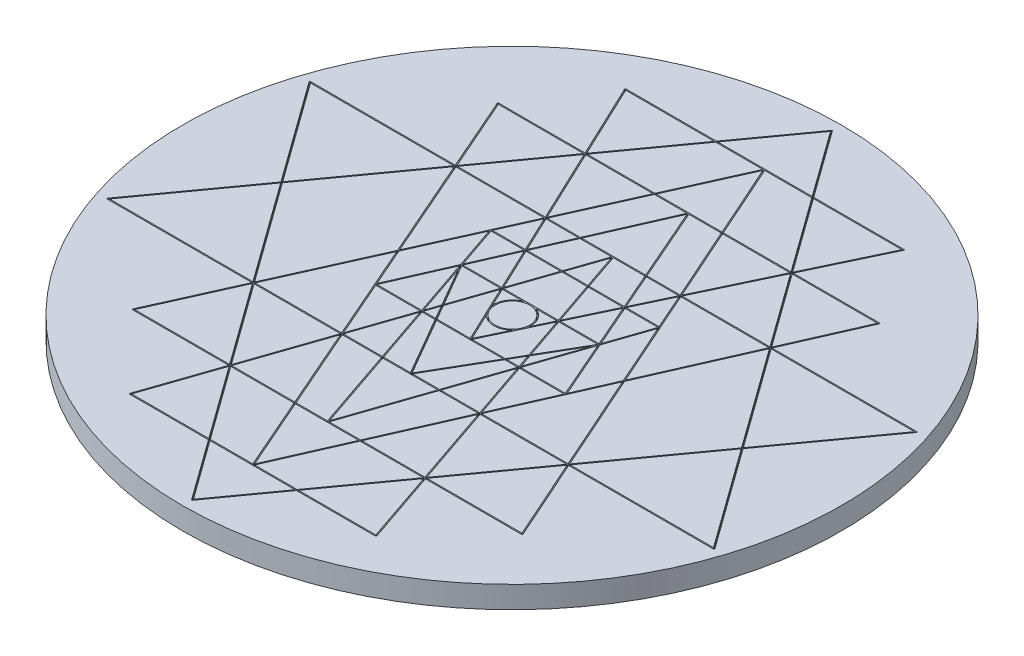
SolidWorks part; units mm, degrees
ref_plane "Front Plane" through (0, 0, 0) normal (0, 0, 1) x (1, 0, 0)
ref_plane "Top Plane" through (0, 0, 0) normal (0, 1, 0) x (1, 0, 0)
ref_plane "Right Plane" through (0, 0, 0) normal (1, 0, 0) x (0, 0, -1)
sketch "Sketch1" plane through (0, 0, 0) normal (0, 1, 0) x (1, 0, 0)
  line L7 (-124.1807, -41.4) -> (124.1807, -41.4)
  line L8 (124.1807, -41.4) -> (0, 130.9)
  line L12 (0, 130.9) -> (-124.1807, -41.4)
  line L13 (-124.1807, 41.4) -> (0, -130.9)
  line L25 (0, -130.9) -> (124.1807, 41.4)
  line L26 (124.1807, 41.4) -> (-124.1807, 41.4)
  line L27 (0, 130.9) -> (0, -130.9) construction
  line L28 (-130.9, 0) -> (130.9, 0) construction
  line L29 (56.9436, 103.3919) -> (-56.9436, 103.3919)
  line L30 (50.3636, -106.0481) -> (-50.3636, -106.0481)
  line L31 (0, 103.3919) -> (-79.6958, -75.4988)
  line L32 (0, 103.3919) -> (79.6958, -75.4988)
  line L33 (0, -106.0481) -> (-78.0225, 72.2994)
  line L34 (-78.0225, 72.2994) -> (0, -106.0481)
  line L35 (0, -106.0481) -> (78.0225, 72.2994)
  line L36 (50.3636, -106.0481) -> (0, 41.4)
  line L37 (0, 41.4) -> (-50.3636, -106.0481)
  line L38 (-38.9651, -16.9798) -> (38.9651, -16.9798)
  line L39 (56.9436, 103.3919) -> (0, -16.9798)
  line L40 (0, -16.9798) -> (-56.9436, 103.3919)
  line L41 (-78.0225, 72.2994) -> (78.0225, 72.2994)
  line L42 (0, 72.2994) -> (-38.9651, -16.9798)
  line L43 (0, 72.2994) -> (38.9651, -16.9798)
  line L44 (-34.5395, 25.8623) -> (34.5395, 25.8623)
  line L45 (-79.6958, -75.4988) -> (79.6958, -75.4988)
  line L46 (-34.5395, 25.8623) -> (0, -75.4988)
  line L47 (0, -75.4988) -> (34.5395, 25.8623)
  line L48 (-28.2818, 7.4983) -> (28.2818, 7.4983)
  line L49 (28.2818, 7.4983) -> (0, -41.4)
  line L50 (0, -41.4) -> (-28.2818, 7.4983)
  line L51 (0, -130.9) -> (124.1807, 41.4) construction
  line L52 (-0.2028, -130.7538) -> (123.9779, 41.5462)
  line L53 (0.2028, -131.0462) -> (124.3835, 41.2538)
  line L54 (124.1807, 41.4) -> (-124.1807, 41.4) construction
  line L55 (124.1807, 41.15) -> (-124.1807, 41.15)
  line L56 (124.1807, 41.65) -> (-124.1807, 41.65)
  line L57 (-124.1807, 41.4) -> (0, -130.9) construction
  line L58 (-123.9779, 41.5462) -> (0.2028, -130.7538)
  line L59 (-124.3835, 41.2538) -> (-0.2028, -131.0462)
  line L60 (0, 130.9) -> (124.1807, -41.4) construction
  line L61 (0.2028, 131.0462) -> (124.3835, -41.2538)
  line L62 (-0.2028, 130.7538) -> (123.9779, -41.5462)
  line L63 (0, 130.9) -> (-124.1807, -41.4) construction
  line L64 (0.2028, 130.7538) -> (-123.9779, -41.5462)
  line L65 (-0.2028, 131.0462) -> (-124.3835, -41.2538)
  line L66 (-124.1807, -41.4) -> (124.1807, -41.4) construction
  line L67 (-124.1807, -41.15) -> (124.1807, -41.15)
  line L68 (-124.1807, -41.65) -> (124.1807, -41.65)
  line L69 (50.3636, -106.0481) -> (0, 41.4) construction
  line L70 (50.1271, -106.1289) -> (-0.2366, 41.3192)
  line L71 (50.6002, -105.9673) -> (0.2366, 41.4808)
  line L72 (0, 41.4) -> (-50.3636, -106.0481) construction
  line L73 (0.2366, 41.3192) -> (-50.1271, -106.1289)
  line L74 (-0.2366, 41.4808) -> (-50.6002, -105.9673)
  line L75 (-50.3636, -106.0481) -> (50.3636, -106.0481) construction
  line L76 (-50.3636, -105.7981) -> (50.3636, -105.7981)
  line L77 (-50.3636, -106.2981) -> (50.3636, -106.2981)
  line L78 (79.6958, -75.4988) -> (0, 103.3919) construction
  line L79 (79.4674, -75.6005) -> (-0.2284, 103.2902)
  line L80 (79.9242, -75.3971) -> (0.2284, 103.4937)
  line L81 (0, 103.3919) -> (-79.6958, -75.4988) construction
  line L82 (0.2284, 103.2902) -> (-79.4674, -75.6005)
  line L83 (-0.2284, 103.4937) -> (-79.9242, -75.3971)
  line L84 (-79.6958, -75.4988) -> (79.6958, -75.4988) construction
  line L85 (-79.6958, -75.2488) -> (79.6958, -75.2488)
  line L86 (-79.6958, -75.7488) -> (79.6958, -75.7488)
  line L87 (0, -106.0481) -> (78.0225, 72.2994) construction
  line L88 (-0.229, -105.9479) -> (77.7935, 72.3996)
  line L89 (0.229, -106.1483) -> (78.2515, 72.1992)
  line L90 (78.0225, 72.2994) -> (-78.0225, 72.2994) construction
  line L91 (78.0225, 72.0494) -> (-78.0225, 72.0494)
  line L92 (78.0225, 72.5494) -> (-78.0225, 72.5494)
  line L93 (-78.0225, 72.2994) -> (0, -106.0481) construction
  line L94 (-77.7935, 72.3996) -> (0.229, -105.9479)
  line L95 (-78.2515, 72.1992) -> (-0.229, -106.1483)
  line L96 (0, -75.4988) -> (34.5395, 25.8623) construction
  line L97 (-0.2366, -75.4182) -> (34.3028, 25.9429)
  line L98 (0.2366, -75.5794) -> (34.7761, 25.7816)
  line L99 (34.5395, 25.8623) -> (-34.5395, 25.8623) construction
  line L100 (34.5395, 25.6123) -> (-34.5395, 25.6123)
  line L101 (34.5395, 26.1123) -> (-34.5395, 26.1123)
  line L102 (-34.5395, 25.8623) -> (0, -75.4988) construction
  line L103 (-34.3028, 25.9429) -> (0.2366, -75.4182)
  line L104 (-34.7761, 25.7816) -> (-0.2366, -75.5794)
  line L105 (38.9651, -16.9798) -> (-38.9651, -16.9798) construction
  line L106 (38.9651, -17.2298) -> (-38.9651, -17.2298)
  line L107 (38.9651, -16.7298) -> (-38.9651, -16.7298)
  line L108 (-38.9651, -16.9798) -> (0, 72.2994) construction
  line L109 (-39.1942, -16.8798) -> (-0.2291, 72.3994)
  line L110 (-38.736, -17.0798) -> (0.2291, 72.1994)
  line L111 (0, 72.2994) -> (38.9651, -16.9798) construction
  line L112 (0.2291, 72.3994) -> (39.1942, -16.8798)
  line L113 (-0.2291, 72.1994) -> (38.736, -17.0798)
  line L114 (56.9436, 103.3919) -> (0, -16.9798) construction
  line L115 (57.1695, 103.285) -> (0.226, -17.0867)
  line L116 (56.7176, 103.4988) -> (-0.226, -16.8729)
  line L117 (0, -16.9798) -> (-56.9436, 103.3919) construction
  line L118 (-0.226, -17.0867) -> (-57.1695, 103.285)
  line L119 (0.226, -16.8729) -> (-56.7176, 103.4988)
  line L120 (-56.9436, 103.3919) -> (56.9436, 103.3919) construction
  line L121 (-56.9436, 103.6419) -> (56.9436, 103.6419)
  line L122 (-56.9436, 103.1419) -> (56.9436, 103.1419)
  line L123 (-28.2818, 7.4983) -> (0, -41.4) construction
  line L124 (-28.0654, 7.6235) -> (0.2164, -41.2748)
  line L125 (-28.4982, 7.3732) -> (-0.2164, -41.5252)
  line L126 (0, -41.4) -> (28.2818, 7.4983) construction
  line L127 (-0.2164, -41.2748) -> (28.0654, 7.6235)
  line L128 (0.2164, -41.5252) -> (28.4982, 7.3732)
  line L129 (28.2818, 7.4983) -> (-28.2818, 7.4983) construction
  line L130 (28.2818, 7.2483) -> (-28.2818, 7.2483)
  line L131 (28.2818, 7.7483) -> (-28.2818, 7.7483)
  circle A1 centre (0, 0) radius 130.9
  circle A3 centre (0, 0.1662) radius 7.3321
  arc A4 (-0.2028, -130.7538) -> (0.2028, -131.0462) centre (0, -130.9) ccw
  arc A5 (124.3835, 41.2538) -> (123.9779, 41.5462) centre (124.1807, 41.4) ccw
  arc A6 (124.1807, 41.15) -> (124.1807, 41.65) centre (124.1807, 41.4) ccw
  arc A7 (-124.1807, 41.65) -> (-124.1807, 41.15) centre (-124.1807, 41.4) ccw
  arc A8 (-123.9779, 41.5462) -> (-124.3835, 41.2538) centre (-124.1807, 41.4) ccw
  arc A9 (-0.2028, -131.0462) -> (0.2028, -130.7538) centre (0, -130.9) ccw
  arc A10 (0.2028, 131.0462) -> (-0.2028, 130.7538) centre (0, 130.9) ccw
  arc A11 (123.9779, -41.5462) -> (124.3835, -41.2538) centre (124.1807, -41.4) ccw
  arc A12 (0.2028, 130.7538) -> (-0.2028, 131.0462) centre (0, 130.9) ccw
  arc A13 (-124.3835, -41.2538) -> (-123.9779, -41.5462) centre (-124.1807, -41.4) ccw
  arc A14 (-124.1807, -41.15) -> (-124.1807, -41.65) centre (-124.1807, -41.4) ccw
  arc A15 (124.1807, -41.65) -> (124.1807, -41.15) centre (124.1807, -41.4) ccw
  arc A16 (50.1271, -106.1289) -> (50.6002, -105.9673) centre (50.3636, -106.0481) ccw
  arc A17 (0.2366, 41.4808) -> (-0.2366, 41.3192) centre (0, 41.4) ccw
  arc A18 (0.2366, 41.3192) -> (-0.2366, 41.4808) centre (0, 41.4) ccw
  arc A19 (-50.6002, -105.9673) -> (-50.1271, -106.1289) centre (-50.3636, -106.0481) ccw
  arc A20 (-50.3636, -105.7981) -> (-50.3636, -106.2981) centre (-50.3636, -106.0481) ccw
  arc A21 (50.3636, -106.2981) -> (50.3636, -105.7981) centre (50.3636, -106.0481) ccw
  arc A22 (79.4674, -75.6005) -> (79.9242, -75.3971) centre (79.6958, -75.4988) ccw
  arc A23 (0.2284, 103.4937) -> (-0.2284, 103.2902) centre (0, 103.3919) ccw
  arc A24 (0.2284, 103.2902) -> (-0.2284, 103.4937) centre (0, 103.3919) ccw
  arc A25 (-79.9242, -75.3971) -> (-79.4674, -75.6005) centre (-79.6958, -75.4988) ccw
  arc A26 (-79.6958, -75.2488) -> (-79.6958, -75.7488) centre (-79.6958, -75.4988) ccw
  arc A27 (79.6958, -75.7488) -> (79.6958, -75.2488) centre (79.6958, -75.4988) ccw
  arc A28 (-0.229, -105.9479) -> (0.229, -106.1483) centre (0, -106.0481) ccw
  arc A29 (78.2515, 72.1992) -> (77.7935, 72.3996) centre (78.0225, 72.2994) ccw
  arc A30 (78.0225, 72.0494) -> (78.0225, 72.5494) centre (78.0225, 72.2994) ccw
  arc A31 (-78.0225, 72.5494) -> (-78.0225, 72.0494) centre (-78.0225, 72.2994) ccw
  arc A32 (-77.7935, 72.3996) -> (-78.2515, 72.1992) centre (-78.0225, 72.2994) ccw
  arc A33 (-0.229, -106.1483) -> (0.229, -105.9479) centre (0, -106.0481) ccw
  arc A34 (-0.2366, -75.4182) -> (0.2366, -75.5794) centre (0, -75.4988) ccw
  arc A35 (34.7761, 25.7816) -> (34.3028, 25.9429) centre (34.5395, 25.8623) ccw
  arc A36 (34.5395, 25.6123) -> (34.5395, 26.1123) centre (34.5395, 25.8623) ccw
  arc A37 (-34.5395, 26.1123) -> (-34.5395, 25.6123) centre (-34.5395, 25.8623) ccw
  arc A38 (-34.3028, 25.9429) -> (-34.7761, 25.7816) centre (-34.5395, 25.8623) ccw
  arc A39 (-0.2366, -75.5794) -> (0.2366, -75.4182) centre (0, -75.4988) ccw
  arc A40 (38.9651, -17.2298) -> (38.9651, -16.7298) centre (38.9651, -16.9798) ccw
  arc A41 (-38.9651, -16.7298) -> (-38.9651, -17.2298) centre (-38.9651, -16.9798) ccw
  arc A42 (-39.1942, -16.8798) -> (-38.736, -17.0798) centre (-38.9651, -16.9798) ccw
  arc A43 (0.2291, 72.1994) -> (-0.2291, 72.3994) centre (0, 72.2994) ccw
  arc A44 (0.2291, 72.3994) -> (-0.2291, 72.1994) centre (0, 72.2994) ccw
  arc A45 (38.736, -17.0798) -> (39.1942, -16.8798) centre (38.9651, -16.9798) ccw
  arc A46 (57.1695, 103.285) -> (56.7176, 103.4988) centre (56.9436, 103.3919) ccw
  arc A47 (-0.226, -16.8729) -> (0.226, -17.0867) centre (0, -16.9798) ccw
  arc A48 (-0.226, -17.0867) -> (0.226, -16.8729) centre (0, -16.9798) ccw
  arc A49 (-56.7176, 103.4988) -> (-57.1695, 103.285) centre (-56.9436, 103.3919) ccw
  arc A50 (-56.9436, 103.6419) -> (-56.9436, 103.1419) centre (-56.9436, 103.3919) ccw
  arc A51 (56.9436, 103.1419) -> (56.9436, 103.6419) centre (56.9436, 103.3919) ccw
  arc A52 (-28.0654, 7.6235) -> (-28.4982, 7.3732) centre (-28.2818, 7.4983) ccw
  arc A53 (-0.2164, -41.5252) -> (0.2164, -41.2748) centre (0, -41.4) ccw
  arc A54 (-0.2164, -41.2748) -> (0.2164, -41.5252) centre (0, -41.4) ccw
  arc A55 (28.4982, 7.3732) -> (28.0654, 7.6235) centre (28.2818, 7.4983) ccw
  arc A56 (28.2818, 7.2483) -> (28.2818, 7.7483) centre (28.2818, 7.4983) ccw
  arc A57 (-28.2818, 7.7483) -> (-28.2818, 7.2483) centre (-28.2818, 7.4983) ccw
  circle A60 centre (0, 0) radius 135
  circle A61 centre (0, 0.1662) radius 7.0821
  circle A62 centre (0, 0.1662) radius 7.5821
  point P2 (27.6174, 41.4)
  point P11 (-94.3427, 0)
  point P12 (94.3427, 0)
  point P16 (0, 103.3919)
  point P19 (0, -106.0481)
  point P21 (-64.5048, -41.4)
  point P22 (-64.5048, 41.4)
  point P23 (64.5048, 41.4)
  point P24 (64.5048, -41.4)
  point P25 (-28.2819, -41.4)
  point P30 (28.2819, -41.4)
  point P34 (-27.6174, 41.4)
  point P35 (42.2348, 72.2994)
  point P36 (-20.2671, 25.8623)
  point P37 (-42.2348, 72.2994)
  point P41 (20.2671, 25.8623)
  point P42 (19.9407, -16.9798)
  point P43 (-19.9407, -16.9798)
  point P46 (39.929, -75.4988)
  point P47 (-39.929, -75.4988)
  point P48 (11.5797, 7.4983)
  point P51 (-11.5797, 7.4983)
  point P54 (62.0904, -44.75)
  point P60 (0, 41.4)
  point P67 (-62.0904, -44.75)
  point P74 (62.0904, 44.75)
  point P79 (-62.0904, 44.75)
  point P85 (0, -41.4)
  point P92 (25.1818, -32.324)
  point P97 (-25.1818, -32.324)
  point P103 (0, -106.0481)
  point P110 (39.8479, 13.9466)
  point P115 (-39.8479, 13.9466)
  point P121 (0, -75.4988)
  point P128 (124.3269, 41.6028)
  point P129 (39.0113, -16.8743)
  point P134 (0, 72.2994)
  point P140 (-39.0113, -16.8743)
  point P147 (17.2697, -24.8183)
  point P152 (0, 25.8623)
  point P158 (-17.2697, -24.8183)
  point P165 (0, -16.9798)
  point P170 (-19.4825, 27.6598)
  point P176 (19.4825, 27.6598)
  point P183 (28.4718, 43.2061)
  point P188 (-28.4718, 43.2061)
  point P194 (0, 103.3919)
  point P201 (-14.1409, -16.9508)
  point P206 (14.1409, -16.9508)
  point P212 (0, 7.4983)
  dimension "D1" = 261.8
  dimension "D3" = 209.44
  dimension "D5" = 270
  dimension "D2" = 82.8
  dimension "D4" = 0.5
extrude "Boss-Extrude3" add sketch "Sketch1" along normal blind 9 contours A61 | A62 L116 L130 | A62 L130 L119 | A62 L119 L116 | L107 L127 L70 L115 | L73 L124 L107 L118 | L125 L73 L107 | L128 L107 L70 | L128 L71 L97 | L127 L130 L71 | L74 L130 L124 | L125 L103 L74 | L131 L118 L110 | L110 L107 L104 | L131 L70 L100 L73 | L119 L74 L100 | L116 L100 L71 | L131 L113 L115 | L113 L98 L107 | L128 L67 L97 L106 | L124 L127 L106 | L125 L106 L103 L67 | L104 L73 L67 | L74 L106 L94 | L94 L109 L104 L82 | L103 L109 L100 | L101 L70 L73 | L113 L55 L71 L101 | L100 L112 L97 | L98 L112 L88 L79 | L88 L106 L71 | L98 L67 L70 | L98 L85 L88 L68 | L71 L52 L68 | L89 L67 L79 | L89 L85 L70 | L68 L103 L97 | L104 L68 L94 L85 | L95 L73 L85 | L74 L68 L58 | L82 L85 L59 | L53 L85 L79 | L95 L82 L67 | L95 L64 L58 L83 | L64 L67 L59 | L65 L55 L58 | L55 L94 L83 | L56 L118 L64 | L91 L94 L65 | L119 L83 L91 | L56 L109 L91 L82 | L119 L109 L55 | L101 L118 L82 | L110 L101 L74 L55 | L113 L110 L56 | L91 L112 L56 L79 | L116 L55 L112 | L116 L91 L80 | L62 L115 L56 | L79 L115 L101 | L80 L88 L55 | L89 L80 L52 L62 | L53 L67 L62 | L55 L61 L52 | L88 L91 L61 | L122 L61 L116 | L122 L80 L92 L62 | L64 L121 L62 | L92 L79 L82 | L122 L64 L92 L83 | L122 L119 L65 | A49 L121 L65 A1 L56 L95 A31 L92 L118 | L59 A1 L65 | A25 L83 L68 A1 L59 L77 A19 L74 L86 | L73 L76 L59 | L95 L86 L58 L76 | L77 L58 L52 | L86 L94 L88 | L89 L76 L52 L86 | L53 L76 L70 | A22 L86 L71 A16 L77 L53 A1 L68 L80 | L61 A1 L53 | A60 A13 L65 A1 L59 A7 L56 A10 L61 A5 L53 A11 L68 A4 | A46 L115 L92 A29 L89 L56 A1 L61 L121 region at (-94.3427, 0, 27.5759) region at (-117.2906, 0, 0) region at (-69.7522, 0, 84.0712) region at (-68.3646, 0, 0.0484) region at (-94.3427, 0, -27.5759) region at (-61.3938, 0, 64.1322) region at (-69.6322, 0, -83.9176) region at (-36.0875, 0, 95.8779) region at (0, 0, 114.3562) region at (69.7522, 0, 84.0712) region at (-44.219, 0, 52.7533) region at (-46.3382, 0, 27.7651) region at (-18.3535, 0, 89.7893) region at (-46.1172, 0, -27.5142) region at (36.0875, 0, 95.8779) region at (-37.0679, 0, -4.067) region at (-44.7694, 0, -51.7032) region at (-61.6049, 0, -62.0002) region at (69.6322, 0, -83.9176) region at (-39.6842, 0, -93.0244) region at (0, 0, -112.5854) region at (18.3535, 0, 89.7893) region at (117.2906, 0, 0) region at (-29.0612, 0, 25.0568) region at (-27.1931, 0, 64.1957) region at (61.3938, 0, 64.1322) region at (94.3427, 0, 27.5759) region at (-13.5566, 0, 57.8209) region at (-19.9473, 0, 33.3514) region at (-19.4929, 0, -86.9332) region at (0, 0, 85.6406) region at (-27.4756, 0, -31.0085) region at (39.6842, 0, -93.0244) region at (27.1931, 0, 64.1957) region at (44.219, 0, 52.7533) region at (68.3646, 0, 0.0484) region at (94.3427, 0, -27.5759) region at (-29.0613, 0, 8.884) region at (-27.6974, 0, -19.8046) region at (-27.9003, 0, -62.0326) region at (19.4929, 0, -86.9332) region at (46.3382, 0, 27.7651) region at (-10.7957, 0, 30.5776) region at (0, 0, 52.6746) region at (-20.4555, 0, -36.2554) region at (-13.7611, 0, -56.7978) region at (61.6049, 0, -62.0002) region at (13.5566, 0, 57.8209) region at (-17.2903, 0, 14.906) region at (0, 0, -82.6255) region at (46.1172, 0, -27.5142) region at (-21.7399, 0, 7.2393) region at (-20.0441, 0, -13.585) region at (44.7694, 0, -51.7032) region at (27.9003, 0, -62.0326) region at (37.0679, 0, -4.067) region at (-9.8115, 0, -33.5005) region at (0, 0, -51.6582) region at (29.0612, 0, 25.0568) region at (0, 0, 25.1201)
sketch "Sketch4" plane through (0, 0, 0) normal (0, -1, 0) x (1, 0, 0)
  circle A0 centre (0, 0) radius 135
extrude "Boss-Extrude4" add sketch "Sketch4" against normal blind 8
sketch "Sketch5" plane through (0, 8, 0) normal (0, 1, 0) x (1, 0, 0)
  line L0 (-124.1807, 41.4) -> (124.1807, 41.4) construction
  line L1 (124.1807, 41.4) -> (0, -130.9) construction
  line L2 (0, -130.9) -> (-124.1807, 41.4) construction
  line L3 (-124.1807, -41.4) -> (0, 130.9) construction
  line L6 (0, 130.9) -> (124.1807, -41.4) construction
  line L7 (124.1807, -41.4) -> (-124.1807, -41.4) construction
  line L8 (-50.3636, -106.0481) -> (50.3636, -106.0481) construction
  line L9 (50.3636, -106.0481) -> (0, 41.4) construction
  line L10 (0, 41.4) -> (-50.3636, -106.0481) construction
  line L11 (0, -106.0481) -> (-78.0225, 72.2994) construction
  line L12 (-78.0225, 72.2994) -> (78.0225, 72.2994) construction
  line L13 (78.0225, 72.2994) -> (0, -106.0481) construction
  line L14 (-79.6958, -75.4988) -> (79.6958, -75.4988) construction
  line L15 (79.6958, -75.4988) -> (0, 103.3919) construction
  line L16 (0, 103.3919) -> (-79.6958, -75.4988) construction
  line L17 (56.9436, 103.3919) -> (-56.9436, 103.3919) construction
  line L18 (0, -75.4988) -> (-34.5395, 25.8623) construction
  line L19 (-34.5395, 25.8623) -> (34.5395, 25.8623) construction
  line L20 (34.5395, 25.8623) -> (0, -75.4988) construction
  line L21 (-20.6619, 26.1123) -> (-34.1544, 26.1123) construction
  line L22 (-38.9651, -16.9798) -> (0, 72.2994) construction
  line L23 (0, 72.2994) -> (38.9651, -16.9798) construction
  line L24 (38.9651, -16.9798) -> (-38.9651, -16.9798) construction
  line L25 (-20.29, -16.7298) -> (-38.5832, -16.7298) construction
  circle A0 centre (-64.5048, 41.4) radius 2.5
  circle A1 centre (-64.5048, -41.4) radius 2.5
  circle A2 centre (64.5048, -41.4) radius 2.5
  circle A3 centre (64.5048, 41.4) radius 2.5
  circle A4 centre (-124.1807, 41.4) radius 2.5
  circle A5 centre (-124.1807, -41.4) radius 2.5
  circle A6 centre (124.1807, -41.4) radius 2.5
  circle A7 centre (124.1807, 41.4) radius 2.5
  circle A8 centre (0, -130.9) radius 2.5
  circle A9 centre (0, 130.9) radius 2.5
  circle A10 centre (-50.3636, -106.0481) radius 2.5
  circle A11 centre (50.3636, -106.0481) radius 2.5
  circle A12 centre (0, -106.0481) radius 2.5
  circle A13 centre (0, 103.3919) radius 2.5
  circle A14 centre (94.3427, 0) radius 2.5
  circle A15 centre (56.9436, 103.3919) radius 2.5
  circle A16 centre (-56.9436, 103.3919) radius 2.5
  circle A17 centre (-42.2348, 72.2994) radius 2.5
  circle A18 centre (-39.929, -75.4988) radius 2.5
  circle A19 centre (39.929, -75.4988) radius 2.5
  circle A20 centre (46.2287, -0.3763) radius 2.5
  circle A21 centre (42.2348, 72.2994) radius 2.5
  circle A22 centre (0, 72.2994) radius 2.5
  circle A23 centre (-27.6174, 41.4) radius 2.5
  circle A24 centre (-34.5395, 25.8623) radius 2.5
  circle A25 centre (-28.2818, 7.4983) radius 2.5
  circle A26 centre (-38.9651, -16.9798) radius 2.5
  circle A27 centre (-28.2819, -41.4) radius 2.5
  circle A28 centre (0, -75.4988) radius 2.5
  circle A29 centre (28.2819, -41.4) radius 2.5
  circle A30 centre (38.9651, -16.9798) radius 2.5
  circle A31 centre (28.2818, 7.4983) radius 2.5
  circle A32 centre (34.5395, 25.8623) radius 2.5
  circle A33 centre (27.6174, 41.4) radius 2.5
  point P9 (-64.5048, 41.4)
  point P11 (-64.5048, -41.4)
  point P14 (64.5048, -41.4)
  point P24 (64.5048, 41.4)
  dimension "D1" = 5
  dimension "D2" = 5
  dimension "D3" = 5
  dimension "D4" = 5
  dimension "D5" = 5
  dimension "D6" = 5
  dimension "D7" = 5
  dimension "D8" = 5
  dimension "D9" = 5
  dimension "D10" = 5
  dimension "D11" = 5
  dimension "D12" = 5
  dimension "D13" = 5
  dimension "D14" = 5
  dimension "D15" = 5
  dimension "D16" = 5
  dimension "D17" = 5
  dimension "D18" = 5
  dimension "D19" = 5
  dimension "D20" = 5
  dimension "D21" = 5
  dimension "D22" = 5
  dimension "D23" = 5
  dimension "D25" = 5
  dimension "D26" = 5
  dimension "D28" = 5
  dimension "D29" = 5
  dimension "D30" = 5
  dimension "D31" = 5
  dimension "D32" = 5
  dimension "D33" = 5
  dimension "D34" = 5
  dimension "D35" = 5
  dimension "D36" = 5
  dimension "D24" = 0.25
  dimension "D27" = 0.25
